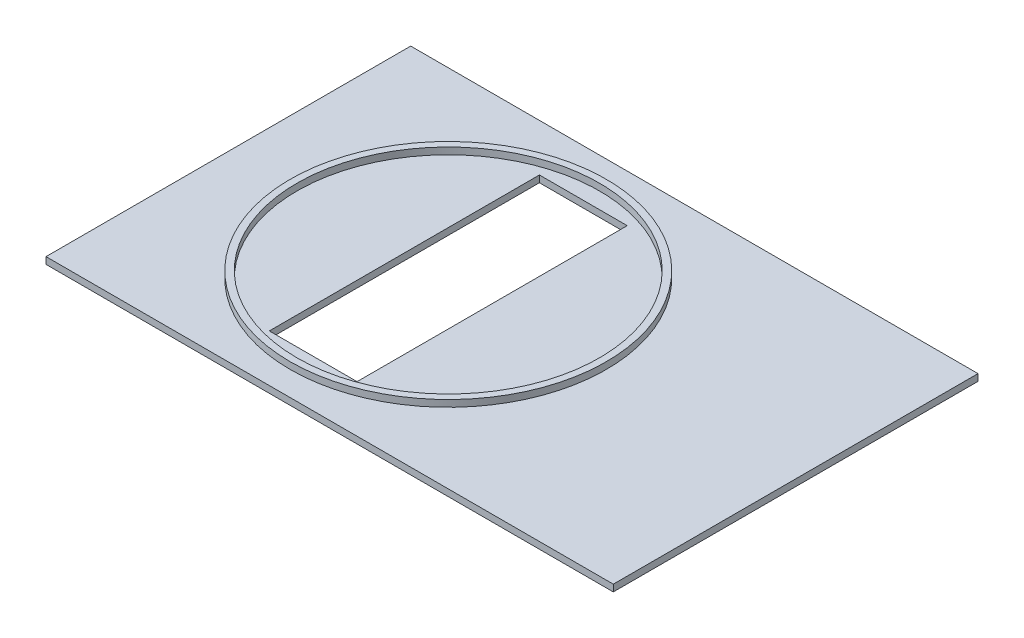
SolidWorks part; units mm, degrees
ref_plane "Front Plane" through (0, 0, 0) normal (0, 0, 1) x (1, 0, 0)
ref_plane "Top Plane" through (0, 0, 0) normal (0, 1, 0) x (1, 0, 0)
ref_plane "Right Plane" through (0, 0, 0) normal (1, 0, 0) x (0, 0, -1)
sketch "Sketch1" plane through (0, 0, 0) normal (0, 1, 0) x (1, 0, 0)
  line L0 (0, 0) -> (0, 270)
  line L3 (-790.1364, 270) -> (-325.6039, 270)
  line L4 (-325.6039, 270) -> (-325.6039, -270)
  line L6 (-325.6039, -270) -> (514.3961, -270)
  line L7 (-790.1364, 270) -> (514.3961, 270)
  line L8 (514.3961, 270) -> (514.3961, -270)
  line L9 (0, -200) -> (-65, -200)
  line L10 (-65, -200) -> (-65, 200)
  line L11 (-65, 200) -> (65, 200)
  line L12 (65, 200) -> (65, -200)
  line L13 (65, -200) -> (0, -200)
  circle A0 centre (0, 0) radius 224
  circle A1 centre (0, 0) radius 234
  dimension "D1" = 840
  dimension "D2" = 448
  dimension "D3" = 468
  dimension "D4" = 540
  dimension "D5" = 270
extrude "Boss-Extrude1" add sketch "Sketch1" against normal blind 10 contours L4 L3 | A1 L6 L8 L7 | A1 A0 | A0 region at (153.9119, 0, -153.9119) region at (160.783, 0, -160.783) region at (257.1981, 0, -260.014)
extrude "Boss-Extrude2" add sketch "Sketch1<3>" along normal blind 10 contours A1 A0 region at (160.783, 0, -160.783)
sketch "Sketch1<3>" plane through (0, 0, 0) normal (0, 1, 0) x (1, 0, 0) same geometry as "Sketch1"
